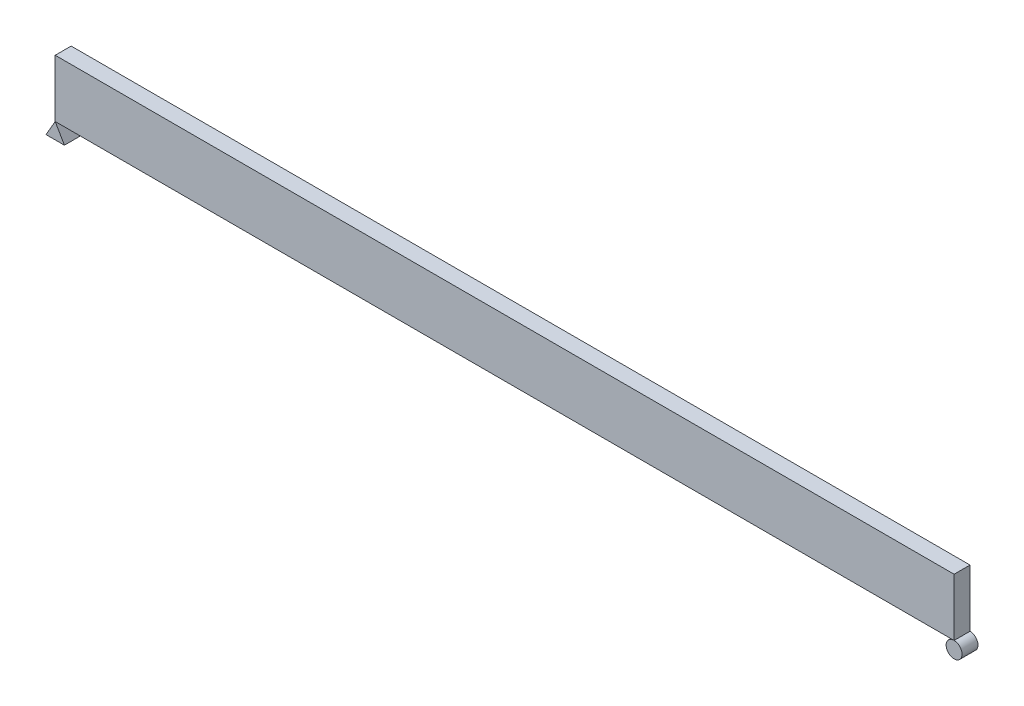
SolidWorks part; units mm, degrees
material "Cast Alloy Steel"
ref_plane "Front Plane" through (0, 0, 0) normal (0, 0, 1) x (1, 0, 0)
ref_plane "Top Plane" through (0, 0, 0) normal (0, 1, 0) x (1, 0, 0)
ref_plane "Right Plane" through (0, 0, 0) normal (1, 0, 0) x (0, 0, -1)
sketch "Sketch1" plane through (0, 0, 0) normal (0, 0, 1) x (1, 0, 0)
  line L1 (-3581.4, 228.6) -> (3581.4, 228.6)
  line L2 (-3581.4, 228.6) -> (-3581.4, -228.6)
  line L3 (-3581.4, -228.6) -> (3581.4, -228.6)
  line L4 (3581.4, 228.6) -> (3581.4, -228.6)
  line L5 (0, -228.6) -> (0, 228.6) construction
  line L6 (-3581.4, 0) -> (3581.4, 0) construction
  line L8 (-3654.7235, -355.6) -> (-3581.4, -228.6)
  line L9 (-3581.4, -228.6) -> (-3508.0765, -355.6)
  line L10 (-3508.0765, -355.6) -> (-3654.7235, -355.6)
  circle A0 centre (3581.4, -292.1) radius 63.5
  point P0 (0, 0)
  dimension "D6" = 127
  dimension "D1" = 457.2
  dimension "D2" = 7162.8
  dimension "D3" = 127
  dimension "D4" = 60
  dimension "D5" = 60
extrude "Boss-Extrude1" add sketch "Sketch1" along normal blind 127 contours L4 L1 L2 L3 | A0 | L9 L10 L8 region at (0, 0, 0)
sketch "Sketch2" plane through (0, 0, 127) normal (0, 0, 1) x (1, 0, 0)
  line L0 (-2667, 648.3464) -> (-2667, 228.6) construction
  line L1 (-3581.4, 228.6) -> (3581.4, 228.6) construction
  line L2 (0, 648.3464) -> (0, 228.6) construction
  line L3 (1905, 648.3464) -> (1905, 228.6) construction
  line L4 (-3581.4, 228.6) -> (-3581.4, -228.6) construction
  line L5 (3581.4, 228.6) -> (3581.4, -228.6) construction
  dimension "D1" = 914.4
  dimension "D2" = 3581.4
  dimension "D3" = 1676.4
sketch3d "3DSketch1"
  line L0 (1905, 228.6, 127) -> (1905, 228.6, 0)
  line L1 (-3581.4, 228.6, 0) -> (3581.4, 228.6, 0) construction
  line L2 (0, 228.6, 127) -> (0, 228.6, 0)
  line L3 (-2667, 228.6, 127) -> (-2667, 228.6, 0)
  line L4 (3581.4, 228.6, 127) -> (3581.4, 228.6, 0) construction
  line L5 (-3581.4, 228.6, 127) -> (-3581.4, 228.6, 0) construction
  point P5 (1905, 228.6, 63.5)
  point P9 (0, 228.6, 63.5)
  point P13 (-2667, 228.6, 63.5)
  point P14 (-2667, 228.6, 63.5)
  point P15 (-2667, 228.6, 63.5)
  dimension "D1" = 1676.4
  dimension "D2" = 3581.4
  dimension "D3" = 914.4
ref_axis "Axis1" through (-2667, 228.6, 63.5) along (0, -1, 0)
ref_axis "Axis2" through (0, 228.6, 63.5) along (0, -1, 0)
ref_axis "Axis3" through (1905, 228.6, 63.5) along (0, -1, 0)
